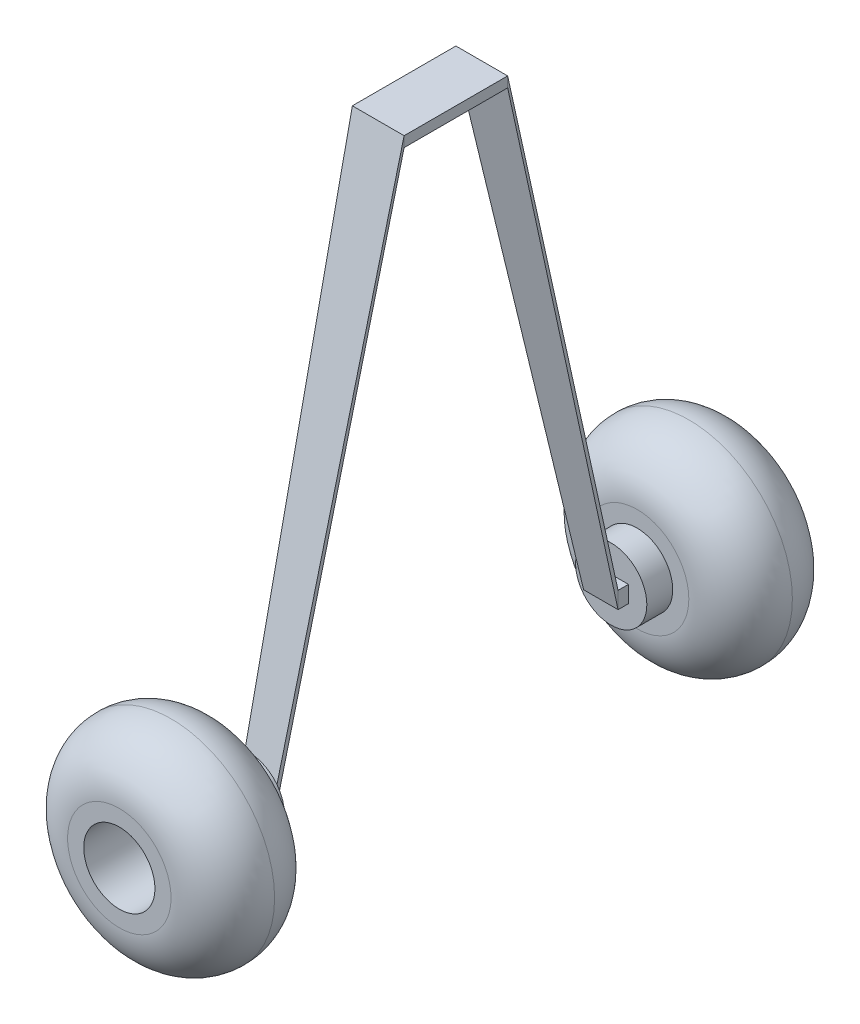
SolidWorks part; units mm, degrees
ref_plane "Front Plane" through (0, 0, 0) normal (0, 0, 1) x (1, 0, 0)
ref_plane "Top Plane" through (0, 0, 0) normal (0, 1, 0) x (1, 0, 0)
ref_plane "Right Plane" through (0, 0, 0) normal (1, 0, 0) x (0, 0, -1)
sketch "Sketch2" plane through (0, 0, 0) normal (0, 0, 1) x (1, 0, 0)
  circle A0 centre (0, 0) radius 19.9881
  circle A1 centre (0, 0) radius 6.8756
sketch "Sketch3" plane through (0, 0, 0) normal (0, 0, 1) x (1, 0, 0)
  circle A0 centre (0, 0) radius 6.8756
ref_plane "Plane3" through (0, 0, -100) normal (0, 0, 1) x (1, 0, 0)
sketch "Sketch4" plane through (0, 0, -100) normal (0, 0, 1) x (1, 0, 0)
  circle A0 centre (0, 0) radius 6.8756
  circle A1 centre (0, 0) radius 19.9881
extrude "Boss-Extrude4" add sketch "Sketch4" along normal blind 20 contours A0 | A1
extrude "Boss-Extrude6" add sketch "Sketch2" along normal blind 20 separate body contours A0 | A1
fillet "Fillet2" radius 10 2 edges at (19.9881, 0, 0) (19.9881, 0, 20)
fillet "Fillet3" radius 10 2 edges at (19.9881, 0, -100) (19.9881, 0, -80)
sketch "Sketch5" plane through (0, 0, -80) normal (0, 0, 1) x (1, 0, 0)
  circle A0 centre (0, 0) radius 6.8756
extrude "Boss-Extrude7" add sketch "Sketch5" along normal blind 5 separate body
sketch "Sketch6" plane through (0, 0, 0) normal (0, 0, -1) x (-1, 0, 0)
  circle A0 centre (0, 0) radius 6.8756
extrude "Boss-Extrude8" add sketch "Sketch6" along normal blind 5 separate body
sketch "Sketch7" plane through (0, 0, -5) normal (0, 0, -1) x (-1, 0, 0)
  line L1 (-3.3234, -1.6155) -> (3.3234, -1.6155)
  line L2 (-3.3234, -1.6155) -> (-3.3234, 1.6155)
  line L3 (-3.3234, 1.6155) -> (3.3234, 1.6155)
  line L4 (3.3234, -1.6155) -> (3.3234, 1.6155)
  line L5 (0, 1.6155) -> (0, -1.6155) construction
  line L6 (-3.3234, 0) -> (3.3234, 0) construction
  point P0 (0, 0)
sketch "Sketch8" plane through (0, 0, -75) normal (0, 0, 1) x (1, 0, 0)
  line L1 (-3.3234, -1.6155) -> (3.3234, -1.6155)
  line L2 (-3.3234, -1.6155) -> (-3.3234, 1.6155)
  line L3 (-3.3234, 1.6155) -> (3.3234, 1.6155)
  line L4 (3.3234, -1.6155) -> (3.3234, 1.6155)
  line L5 (0, 1.6155) -> (0, -1.6155) construction
  line L6 (-3.3234, 0) -> (3.3234, 0) construction
  point P0 (0, 0)
extrude "Boss-Extrude9" add sketch "Sketch7" along normal blind 2 contours L3 L4 L1 L2
extrude "Boss-Extrude10" add sketch "Sketch8" along normal blind 2 contours L3 L4 L1 L2
ref_plane "Plane4" through (0, 100, 0) normal (0, 1, 0) x (1, 0, 0)
sketch "Sketch9" plane through (0, 100, 0) normal (0, 1, 0) x (1, 0, 0)
  line L4 (-5, 30) -> (5, 30)
  line L5 (-5, 30) -> (-5, 50)
  line L6 (-5, 50) -> (5, 50)
  line L7 (5, 30) -> (5, 50)
  line L8 (0, 50) -> (0, 30) construction
  line L9 (-5, 40) -> (5, 40) construction
  point P6 (0, 40)
extrude "Boss-Extrude11" add sketch "Sketch9" against normal blind 2 separate body contours L7 L6 L5 L4
loft "Loft1" add section face at (0, 0, -73) section face at (0, 99, -50) connector at (-3.3234, -1.6155, -73) connector at (-5, 98, -50)
loft "Loft3" add section face at (0, 0, -7) section face at (0, 99, -30) connector at (3.3234, -1.6155, -7) connector at (5, 98, -30)
scale "Scale3" bodies to scale 109 116 107 scale about origin uniform scaling yes scale factor 2
